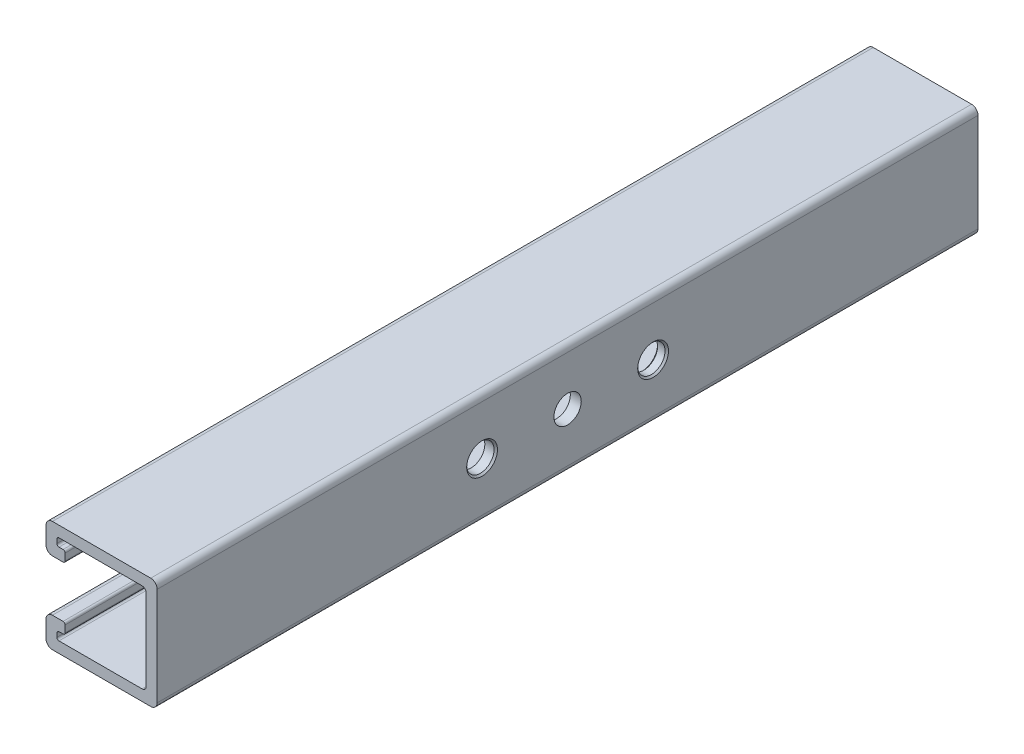
SolidWorks part; units mm, degrees
material "S-Glass Fiber"
ref_plane "Front Plane" through (0, 0, 0) normal (0, 0, 1) x (1, 0, 0)
ref_plane "Top Plane" through (0, 0, 0) normal (0, 1, 0) x (1, 0, 0)
ref_plane "Right Plane" through (0, 0, 0) normal (1, 0, 0) x (0, 0, -1)
sketch "Sketch1" plane through (0, 0, 0) normal (0, 0, 1) x (1, 0, 0)
  line L0 (-13.5255, 9.525) -> (-18.2499, 9.525)
  line L1 (-20.6375, 11.9126) -> (-20.6375, 18.2499)
  line L2 (-18.2499, 20.6375) -> (18.2499, 20.6375)
  line L3 (20.6375, 18.2499) -> (20.6375, -18.2499)
  line L4 (18.2499, -20.6375) -> (-18.2499, -20.6375)
  line L5 (-20.6375, -18.2499) -> (-20.6375, -11.9126)
  line L6 (-18.2499, -9.525) -> (-13.5255, -9.525)
  line L7 (0, 0) -> (20.6375, 0) construction
  line L8 (0, 0) -> (0, 20.6375) construction
  arc A0 (-20.6375, 18.2499) -> (-18.2499, 20.6375) centre (-18.2499, 18.2499) cw
  arc A1 (-18.2499, 9.525) -> (-20.6375, 11.9126) centre (-18.2499, 11.9126) cw
  arc A2 (-20.6375, -11.9126) -> (-18.2499, -9.525) centre (-18.2499, -11.9126) cw
  arc A3 (-18.2499, -20.6375) -> (-20.6375, -18.2499) centre (-18.2499, -18.2499) cw
  arc A4 (20.6375, -18.2499) -> (18.2499, -20.6375) centre (18.2499, -18.2499) cw
  arc A5 (18.2499, 20.6375) -> (20.6375, 18.2499) centre (18.2499, 18.2499) cw
  point P14 (-20.6375, 20.6375)
  point P23 (20.6375, -20.6375)
  point P26 (20.6375, 20.6375)
  dimension "D4" = 2.3876
  dimension "D1" = 41.275
  dimension "D2" = 41.275
  dimension "D3" = 19.05
  dimension "D5" = 7.112
extrude "Extrude-Thin1" add sketch "Sketch1" against normal blind 304.8 thin thin type one direction wall 4.064
fillet "Fillet2" radius 0.762 8 edges at (-16.5735, 13.589, -152.4) (-16.5735, -16.5735, -152.4) (-16.5735, 16.5735, -152.4) (-13.5255, 13.589, -152.4) (-13.5255, 9.525, -152.4) (-13.5255, -9.525, -152.4) (-13.5255, -13.589, -152.4) (-16.5735, -13.589, -152.4)
fillet "Fillet3" radius 1.524 2 edges at (16.5735, 16.5735, -152.4) (16.5735, -16.5735, -152.4)
sketch "Sketch3" plane through (0, 0, 0) normal (1, 0, 0) x (0, 0, -1)
  line L0 (0, 0) -> (304.8, 0) construction
  line L1 (304.8, 18.2499) -> (304.8, -18.2499) construction
  line L2 (0, 0) -> (0, 20.6375) construction
  line L3 (304.8, 0) -> (304.8, 20.6375) construction
  line L4 (304.8, 20.6375) -> (0, 20.6375) construction
  point P3 (101.6, 0)
  point P4 (203.2, 0)
  dimension "D1" = 101.6
  dimension "D2" = 101.6
sketch "Sketch4" plane through (20.6375, 0, 0) normal (1, 0, 0) x (0, 0, -1)
  line L0 (0, 0) -> (304.8, 0) construction
  line L1 (0, 18.2499) -> (0, -18.2499) construction
  line L2 (304.8, 18.2499) -> (304.8, -18.2499) construction
  line L3 (184.15, 5.08) -> (152.4, 5.08) construction
  line L4 (152.4, 5.08) -> (120.65, 5.08) construction
  circle A0 centre (152.4, 0) radius 5.08
  circle A1 centre (184.15, 0) radius 5.08
  circle A2 centre (120.65, 0) radius 5.08
  dimension "D1" = 10.16
  dimension "D2" = 10.16
  dimension "D3" = 31.75
extrude "Cut-Extrude1" cut sketch "Sketch4" against normal through all
chamfer "Chamfer1" distance 0.635 angle 45 3 edges at (20.6375, 0, -125.73) (16.5735, 0, -179.07) (20.6375, 0, -189.23)
